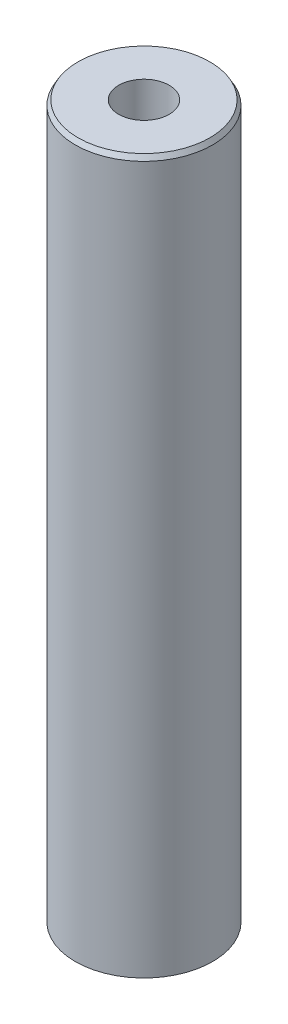
SolidWorks part; units mm, degrees
ref_plane "Front Plane" through (0, 0, 0) normal (0, 0, 1) x (1, 0, 0)
ref_plane "Top Plane" through (0, 0, 0) normal (0, 1, 0) x (1, 0, 0)
ref_plane "Right Plane" through (0, 0, 0) normal (1, 0, 0) x (0, 0, -1)
sketch "Sketch1" plane through (0, 0, 0) normal (0, 1, 0) x (1, 0, 0)
  circle A0 centre (0, 0) radius 55
  dimension "SHAFT_OD" = 110
extrude "Boss-Extrude1" add sketch "Sketch1" along normal blind 572.5824
sketch "Sketch2" plane through (0, 0, 0) normal (0, 1, 0) x (1, 0, 0)
  circle A0 centre (0, 0) radius 20.2277
  dimension "BORE_D" = 40.4555
extrude "Cut-Extrude1" cut sketch "Sketch2" along normal through all
chamfer "Chamfer1" distance 3.8441 angle 30 2 edges at (0, 572.5824, 55) (0, 0, 55) first distance on face at (0, 572.5824, 55) first distance on face at (0, 0, 20.2277)
